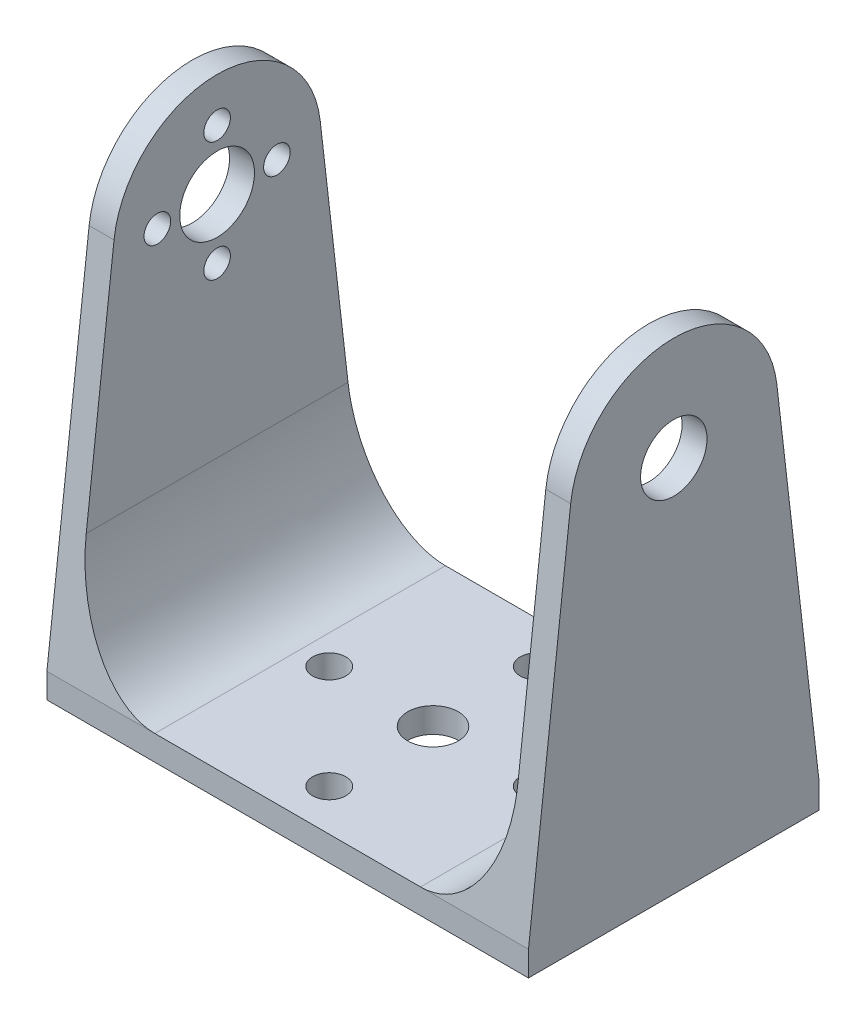
SolidWorks part; units mm, degrees
ref_plane "Plano frontal" through (0, 0, 0) normal (0, 0, 1) x (1, 0, 0)
ref_plane "Plano superior" through (0, 0, 0) normal (0, 1, 0) x (1, 0, 0)
ref_plane "Plano direito" through (0, 0, 0) normal (1, 0, 0) x (0, 0, -1)
sketch "Sketch1" plane through (0, 0, 0) normal (0, 1, 0) x (1, 0, 0)
  line L1 (-29, 17.5) -> (29, 17.5)
  line L2 (-29, 17.5) -> (-29, -17.5)
  line L3 (-29, -17.5) -> (29, -17.5)
  line L4 (29, 17.5) -> (29, -17.5)
  line L5 (-29, 17.5) -> (29, -17.5) construction
  line L6 (-29, -17.5) -> (29, 17.5) construction
  point P0 (0, 0)
  dimension "D1" = 58
  dimension "D2" = 35
extrude "Boss-Extrude1" add sketch "Sketch1" along normal mid plane 3
sketch "Sketch3" plane through (-29, 0, 0) normal (-1, 0, 0) x (0, 0, 1)
  line L0 (-17.5, 1.5) -> (-12.4172, 45.4365)
  line L1 (12.4172, 45.4365) -> (17.5, 1.5)
  line L2 (17.5, 1.5) -> (-17.5, 1.5)
  arc A0 (-12.4172, 45.4365) -> (12.4172, 45.4365) centre (0, 44) cw
  point P5 (0, 56.5)
  point P8 (-17.5, 1.5)
  point P9 (0, 0)
  point P10 (0, 0)
  point P11 (0, 0)
  dimension "D2" = 12.5
  dimension "D1" = 55
extrude "Boss-Extrude2" add sketch "Sketch3" against normal blind 3
sketch "Sketch4" plane through (-29, 0, 0) normal (-1, 0, 0) x (0, 0, 1)
  circle A0 centre (0, 44) radius 4.5
  circle A1 centre (0, 51.2) radius 1.6
  arc A2 (12.4172, 45.4365) -> (-12.4172, 45.4365) centre (0, 44) ccw construction
  point P4 (0, 0)
  dimension "D1" = 9
  dimension "D2" = 3.2
  dimension "D3" = 7.2
extrude "Cut-Extrude1" cut sketch "Sketch4" against normal up to surface (3 mm away) up to face at (-26, 26.2341, 0)
pattern_circular "CirPattern1" count 4 over 360 about axis through (-13.2721, 44, 0) along (-1, 0, 0) of "Cut-Extrude1"
mirror "Mirror1" about plane through (0, 0, 0) normal (1, 0, 0) of "Boss-Extrude2"
sketch "Sketch5" plane through (0, 1.5, 0) normal (0, 1, 0) x (1, 0, 0)
  circle A0 centre (0, 0) radius 3.05
  dimension "D1" = 6.1
extrude "Cut-Extrude2" cut sketch "Sketch5" against normal blind 3
sketch "Sketch6" plane through (0, 1.5, 0) normal (0, 1, 0) x (1, 0, 0)
  circle A0 centre (0, 12.5) radius 2
  circle A1 centre (0, 0) radius 3.05 construction
  point P4 (0, 0)
  point P5 (0, 0)
  point P6 (0, 0)
  dimension "D1" = 4
  dimension "D2" = 12.5
extrude "Cut-Extrude3" cut sketch "Sketch6" against normal up to surface (3 mm away) contours A0 up to face at (0, -1.5, 3.05)
pattern_circular "CirPattern2" count 4 over 360 about axis through (0, -1.5, 0) along (0, 1, 0) of "Cut-Extrude3"
fillet "Fillet1" radius 10 2 edges at (-26, 1.5, 0) (26, 1.5, 0) second distance 15 first distance on face at (0, 1.5, 10.5)
sketch "Sketch8" plane through (29, 0, 0) normal (1, 0, 0) x (0, 0, -1)
  circle A0 centre (0, 44) radius 4
  dimension "D1" = 8
extrude "Cut-Extrude4" cut sketch "Sketch8" against normal up to surface (3 mm away) up to face at (26, 33.7341, -3.1043)
